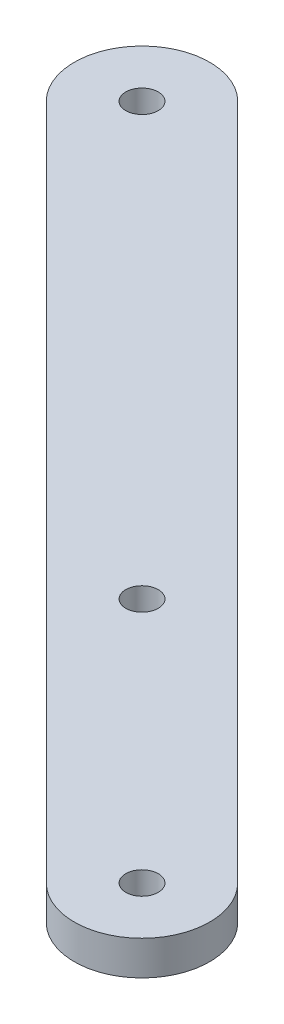
SolidWorks part; units mm, degrees
ref_plane "Front Plane" through (0, 0, 0) normal (0, 0, 1) x (1, 0, 0)
ref_plane "Top Plane" through (0, 0, 0) normal (0, 1, 0) x (1, 0, 0)
ref_plane "Right Plane" through (0, 0, 0) normal (1, 0, 0) x (0, 0, -1)
sketch "Sketch1" plane through (0, 0, 0) normal (0, 1, 0) x (1, 0, 0)
  line L0 (0, 0) -> (-125, 0) construction
  line L1 (0, -12.5) -> (-125, -12.5)
  line L2 (0, 12.5) -> (-125, 12.5)
  line L3 (0, 0) -> (125, -125) construction
  line L4 (8.8388, 8.8388) -> (133.8388, -116.1612)
  line L5 (-8.8388, -8.8388) -> (116.1612, -133.8388)
  line L6 (125, -125) -> (125, 0) construction
  line L7 (125, 0) -> (0, 0) construction
  line L8 (79.583, -79.583) -> (101.8189, -57.3472) construction
  line L9 (101.8189, -57.3472) -> (22.2359, 22.2359) construction
  line L10 (22.2359, 22.2359) -> (0, 0) construction
  arc A0 (0, -12.5) -> (0, 12.5) centre (0, 0) ccw
  arc A1 (-125, 12.5) -> (-125, -12.5) centre (-125, 0) ccw
  arc A2 (8.8388, 8.8388) -> (-8.8388, -8.8388) centre (0, 0) ccw
  arc A3 (116.1612, -133.8388) -> (133.8388, -116.1612) centre (125, -125) ccw
  circle A4 centre (-125, 0) radius 3
  circle A5 centre (0, 0) radius 3
  circle A6 centre (125, -125) radius 3
  circle A7 centre (79.583, -79.583) radius 3
  point P3 (-62.5, 0)
  point P8 (62.5, -62.5)
  dimension "D4" = 6
  dimension "D1" = 125
  dimension "D2" = 125
  dimension "D3" = 25
  dimension "D5" = 112.5474
extrude "Boss-Extrude1" add sketch "Sketch1" along normal mid plane 6.35 contours A0 A2 L5 L1 A5 | L5 A3 L4 A0 L1 A7 A6 region at (69.0732, 0, 69.0604) region at (-2.5888, 0, 12.1464)
fillet "Fillet1" [suppressed] radius 25
